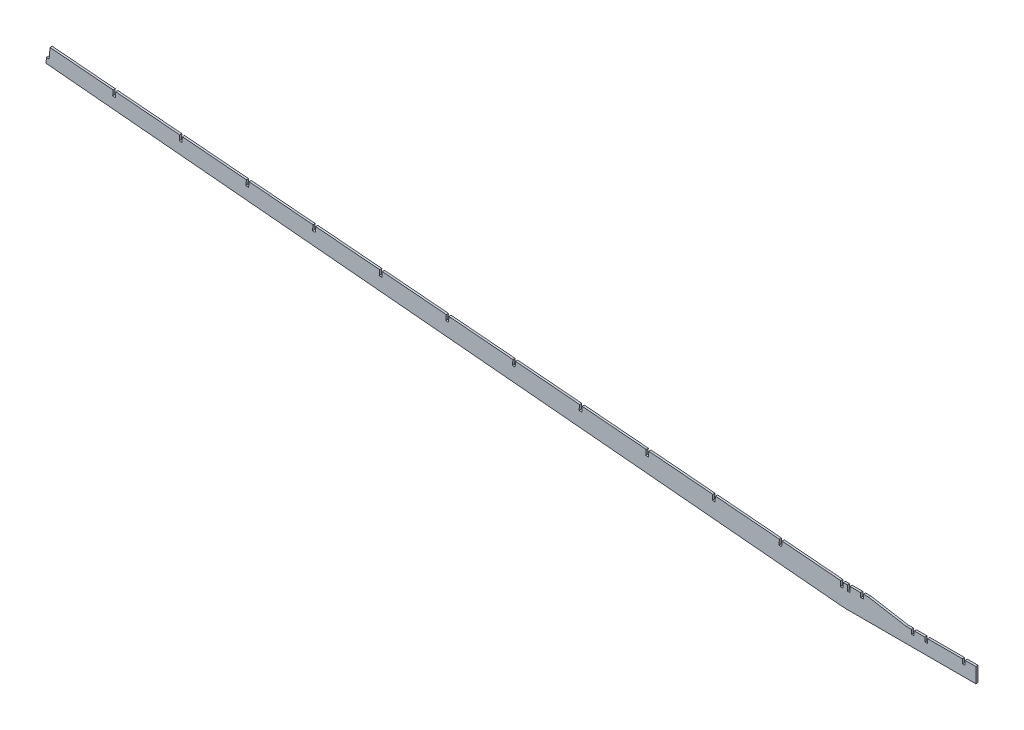
SolidWorks part; units mm, degrees
material "Plywood"
ref_plane "Front Plane" through (0, 0, 0) normal (0, 0, 1) x (1, 0, 0)
ref_plane "Top Plane" through (0, 0, 0) normal (0, 1, 0) x (1, 0, 0)
ref_plane "Right Plane" through (0, 0, 0) normal (1, 0, 0) x (0, 0, -1)
sketch "Sketch1" plane through (0, 0, 0) normal (0, 0, 1) x (1, 0, 0)
  line L0 (-949.6524, 80.0757) -> (-9.8872, -5.2596)
  line L1 (-945.9572, 86.1378) -> (-949.6524, 80.0757)
  line L8 (-6.7234, -5.5253) -> (-5.1293, 13.4579)
  line L9 (-5.1293, 13.4579) -> (-8.2932, 13.7235)
  line L10 (-8.2932, 13.7235) -> (-9.8872, -5.2596)
  line L11 (-9.8872, -5.2596) -> (-6.7234, -5.5253)
  line L12 (3.175, -5.8337) -> (3.175, 13.2163)
  line L13 (3.175, 13.2163) -> (0, 13.2163)
  line L14 (0, 13.2163) -> (0, -5.8337)
  line L15 (0, -5.8337) -> (3.175, -5.8337)
  line L17 (-943.1142, 119.9943) -> (-945.9572, 86.1378)
  line L18 (-945.9572, 86.1378) -> (-9.8872, -5.2596)
  line L19 (-6.7234, -5.5253) -> (0, -5.8337)
  line L20 (3.175, -5.8337) -> (152.4, -5.8337)
  line L21 (152.4, -5.8337) -> (152.4, 11.9463)
  line L22 (152.4, 11.9463) -> (69.85, 11.9463)
  line L23 (69.85, 11.9463) -> (25.4, 19.5663)
  line L24 (25.4, 19.5663) -> (-1.9861, 19.5663)
  line L25 (-1.9861, 19.5663) -> (-944.8986, 98.7448)
  line L26 (0, 13.2163) -> (0, 19.5663)
  line L27 (3.175, 13.2163) -> (3.175, 19.5663)
  line L28 (-5.1293, 13.4579) -> (-4.598, 19.7856)
  line L29 (-8.2932, 13.7235) -> (-7.7618, 20.0513)
  line L30 (-8.2932, 13.7235) -> (-945.4292, 92.426)
  line L31 (15.875, 19.5663) -> (15.875, 14.4863)
  line L32 (15.875, 14.4863) -> (19.05, 14.4863)
  line L33 (19.05, 14.4863) -> (19.05, 19.5663)
  line L34 (76.2, 6.8663) -> (76.2, 11.9463)
  line L35 (76.2, 6.8663) -> (79.375, 6.8663)
  line L36 (79.375, 6.8663) -> (79.375, 11.9463)
  line L37 (92.075, 11.9463) -> (92.075, 6.8663)
  line L38 (92.075, 6.8663) -> (95.25, 6.8663)
  line L39 (95.25, 6.8663) -> (95.25, 11.9463)
  line L40 (136.525, 11.9463) -> (136.525, 6.8663)
  line L41 (136.525, 6.8663) -> (139.7, 6.8663)
  line L42 (139.7, 6.8663) -> (139.7, 11.9463)
  line L44 (-949.6524, 80.0757) -> (-949.1211, 86.4035)
  line L45 (-949.1211, 86.4035) -> (-945.959, 86.1163)
  dimension "D1" = 25.4
  dimension "D2" = 6.35
extrude "Boss-Extrude1" add sketch "Sketch1" along normal blind 2.54 contours L42 L41 L40 L22 L39 L38 L37 L36 L35 L34 L23 L24 L33 L32 L31 L27 L12 L20 L21 | L30 L29 L25 L17 | L28 L8 L19 L14 L26 L24 L25 | L10 L11 L8 L9 | L14 L15 L12 L13 | L45 L44 L17 | L10 L30 L17 L18 | L18 L1 L0 region at (-635.1656, 53.6513, 0) region at (-948.2478, 84.1988, 0) region at (-398.9758, 39.6362, 0) region at (-7.5083, 4.0991, 0) region at (-476.4854, 56.2272, 0) region at (-2.8648, 6.1846, 0) region at (1.5875, 3.6913, 0) region at (71.853, 4.2703, 0)
sketch "Sketch2" plane through (0, 0, 2.54) normal (0, 0, 1) x (1, 0, 0)
  line L1 (-76.483, 72.8473) -> (-82.5095, 1.0799)
  line L3 (-155.6446, 77.1971) -> (-161.4339, 8.255)
  line L5 (-234.8005, 81.6162) -> (-240.3617, 15.3891)
  line L7 (-313.9625, 85.9617) -> (-319.2865, 22.5591)
  line L9 (-393.1191, 90.3714) -> (-398.2146, 29.6908)
  line L11 (-472.2837, 94.686) -> (-477.1388, 36.8682)
  line L13 (-551.4418, 99.0783) -> (-556.0668, 44.0001)
  line L15 (-630.6082, 103.3716) -> (-634.991, 51.1773)
  line L17 (-709.7674, 107.7507) -> (-713.9195, 58.3043)
  line L19 (-788.9364, 112.0121) -> (-792.8436, 65.483)
  line L21 (-868.0976, 116.3681) -> (-871.7723, 72.6069)
  line L23 (-73.3191, 72.5816) -> (-79.3456, 0.8143)
  line L25 (-152.4808, 76.9314) -> (-158.27, 7.9893)
  line L27 (-231.6366, 81.3506) -> (-237.1978, 15.1234)
  line L29 (-310.7986, 85.696) -> (-316.1227, 22.2934)
  line L31 (-389.9552, 90.1057) -> (-395.0507, 29.4251)
  line L33 (-469.1198, 94.4203) -> (-473.9749, 36.6025)
  line L35 (-548.2779, 98.8126) -> (-552.903, 43.7344)
  line L37 (-627.4443, 103.1059) -> (-631.8272, 50.9116)
  line L39 (-706.6035, 107.485) -> (-710.7556, 58.0386)
  line L41 (-785.7726, 111.7464) -> (-789.6797, 65.2173)
  line L43 (-864.9337, 116.1024) -> (-868.6084, 72.3413)
  line L45 (-8.2932, 13.7235) -> (-945.4292, 92.426)
  line L47 (-7.7618, 20.0513) -> (-944.8986, 98.7448)
extrude "Cut-Extrude1" cut sketch "Sketch2" against normal through all and the other way through all contours L45 L43 L21 | L45 L41 L19 | L45 L39 L17 | L45 L37 L15 | L45 L35 L13 | L45 L33 L11 | L45 L31 L9 | L45 L29 L7 | L45 L27 L5 | L45 L25 L3 | L45 L23 L1 region at (-79.0879, 22.8549, 2.54) region at (-158.0579, 29.4865, 2.54) region at (-237.0279, 36.1182, 2.54) region at (-315.998, 42.7499, 2.54) region at (-394.968, 49.3816, 2.54) region at (-473.938, 56.0132, 2.54) region at (-552.9081, 62.6449, 2.54) region at (-631.8781, 69.2766, 2.54) region at (-710.8481, 75.9083, 2.54) region at (-789.8182, 82.54, 2.54) region at (-868.7882, 89.1716, 2.54)
move or copy body "Body-Move/Copy1" [suppressed] bodies to move or copy 102 parameters "D1"=0, "D2"=0, "D3"=0
